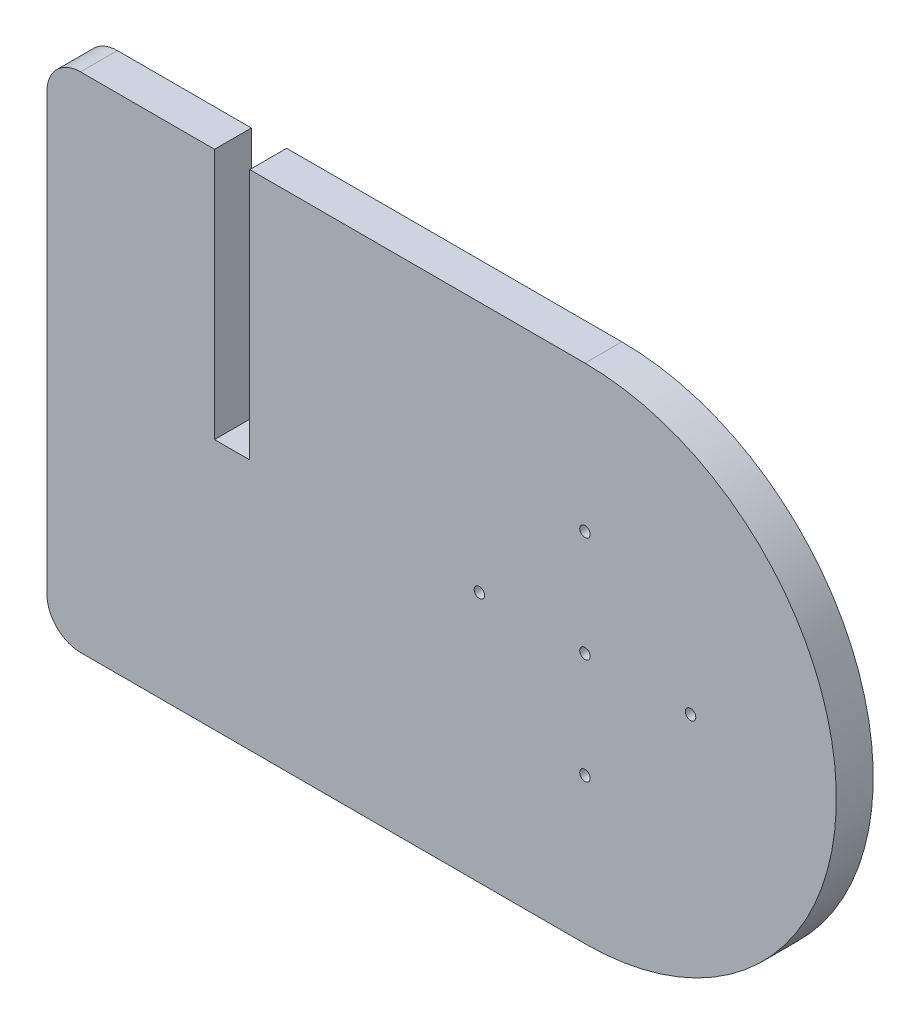
SolidWorks part; units mm, degrees
ref_plane "Front Plane" through (0, 0, 0) normal (0, 0, 1) x (1, 0, 0)
ref_plane "Top Plane" through (0, 0, 0) normal (0, 1, 0) x (1, 0, 0)
ref_plane "Right Plane" through (0, 0, 0) normal (1, 0, 0) x (0, 0, -1)
sketch "Sketch1" plane through (0, 0, 0) normal (0, 0, 1) x (1, 0, 0)
  line L0 (-0.3781, 19.05) -> (25.0219, 19.05)
  line L1 (-15.7451, -19.05) -> (25.0219, -19.05)
  line L2 (-15.7451, -9.525) -> (-15.7451, 19.05)
  line L3 (-15.7451, 19.05) -> (-3.0451, 19.05)
  line L6 (-15.7451, 19.05) -> (0, 0) construction
  line L7 (-15.7451, -9.525) -> (-15.7451, -19.05)
  line L8 (-3.0451, 19.05) -> (-3.0451, 0)
  line L9 (-3.0451, 0) -> (-0.3781, 0)
  line L10 (-0.3781, 19.05) -> (-0.3781, 0)
  arc A0 (25.0219, -19.05) -> (25.0219, 19.05) centre (25.0219, 0) ccw
  circle A1 centre (25.0219, 8) radius 0.3969
  circle A2 centre (25.0219, 0) radius 0.3969
  circle A3 centre (33.0219, 0) radius 0.3969
  circle A4 centre (25.0219, -8) radius 0.3969
  circle A5 centre (17.0219, 0) radius 0.3969
  point P0 (0, 0)
  point P24 (25.0219, 0)
  dimension "D2" = 0.7937
  dimension "D6" = 0.7937
  dimension "D1" = 25.4
  dimension "D3" = 2.667
  dimension "D4" = 12.7
  dimension "D5" = 8
  dimension "D7" = 4
extrude "Boss-Extrude1" add sketch "Sketch1" along normal blind 2.794
fillet "Fillet1" radius 2.54 2 edges at (-15.7451, -19.05, 1.397) (-15.7451, 19.05, 1.397)
